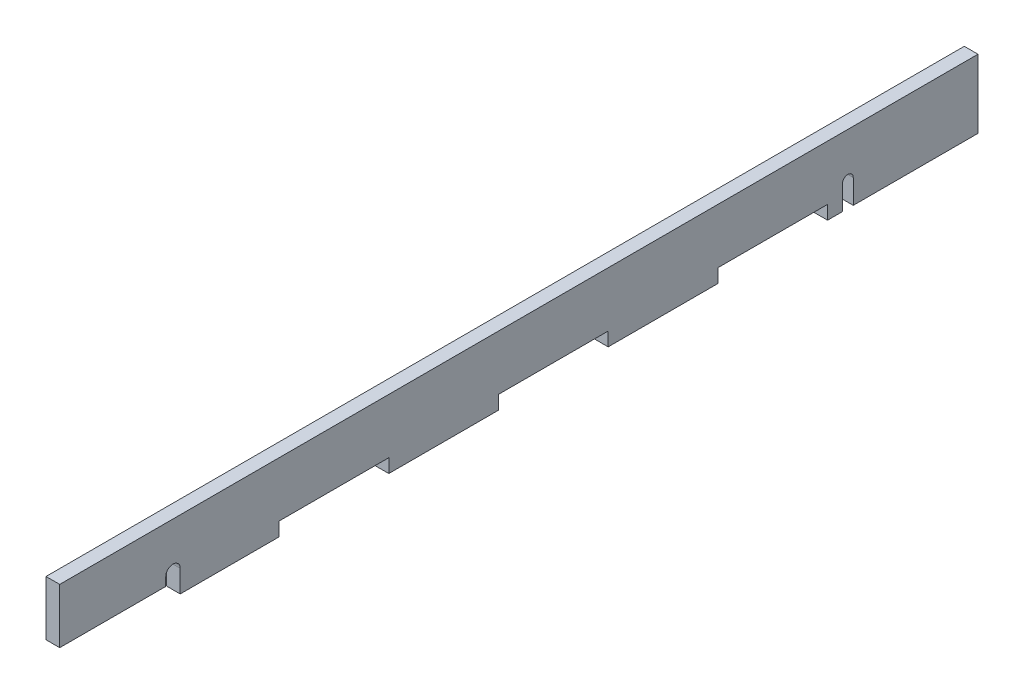
SolidWorks part; units mm, degrees
ref_plane "Front Plane" through (0, 0, 0) normal (0, 0, 1) x (1, 0, 0)
ref_plane "Top Plane" through (0, 0, 0) normal (0, 1, 0) x (1, 0, 0)
ref_plane "Right Plane" through (0, 0, 0) normal (1, 0, 0) x (0, 0, -1)
sketch "Sketch2" plane through (0, 0, 0) normal (1, 0, 0) x (0, 0, -1)
  line L30 (48.3194, 0) -> (99.1194, 0)
  line L31 (-2.4806, 6.35) -> (-2.4806, 31.75)
  line L32 (-2.4806, 31.75) -> (422.7895, 31.75)
  line L33 (422.7895, 0) -> (422.7895, 31.75)
  line L45 (422.7895, 31.75) -> (422.7895, 35.3357) construction
  line L46 (353.1194, 6.35) -> (353.1194, 0)
  line L47 (302.3194, 6.35) -> (353.1194, 6.35)
  line L48 (302.3194, 6.35) -> (302.3194, 0)
  line L49 (251.5194, 6.35) -> (251.5194, 0)
  line L50 (200.7194, 6.35) -> (251.5194, 6.35)
  line L51 (200.7194, 6.35) -> (200.7194, 0)
  line L52 (149.9194, 6.35) -> (149.9194, 0)
  line L53 (99.1194, 6.35) -> (149.9194, 6.35)
  line L54 (99.1194, 6.35) -> (99.1194, 0)
  line L55 (48.3194, 6.35) -> (48.3194, 0)
  line L56 (-2.4806, 6.35) -> (48.3194, 6.35)
  line L57 (353.1194, 0) -> (422.7895, 0)
  line L58 (251.5194, 0) -> (302.3194, 0)
  line L59 (149.9194, 0) -> (200.7194, 0)
  dimension "D1" = 50.8
  dimension "D2" = 6.35
extrude "Boss-Extrude1" add sketch "Sketch2" along normal blind 6.35
sketch "Sketch3" plane through (6.35, 0, 0) normal (1, 0, 0) x (0, 0, -1)
  line L0 (353.1194, 6.35) -> (422.7895, 6.35) construction
  line L1 (422.7895, 0) -> (422.7895, 31.75) construction
  line L2 (362.5194, 8.66) -> (362.5194, 6.35) construction
  line L3 (-2.4806, 31.75) -> (-2.4806, 6.35) construction
  line L5 (365.0194, 11.16) -> (365.0194, -0.0346)
  line L6 (360.0194, 11.16) -> (360.0194, -0.0346)
  line L7 (365.0194, -0.0346) -> (360.0194, -0.0346)
  arc A0 (365.0194, 11.16) -> (360.0194, 11.16) centre (362.5194, 11.16) ccw
  dimension "D1" = 5
  dimension "D2" = 2.31
  dimension "D3" = 365
extrude "Cut-Extrude1" cut sketch "Sketch3" against normal up to next
sketch "Sketch4" plane through (6.35, 0, 0) normal (1, 0, 0) x (0, 0, -1)
  line L1 (53.3194, 10.31) -> (53.3194, 0)
  line L2 (48.3194, 6.35) -> (48.3194, 0)
  line L3 (53.3194, 0) -> (48.3194, 0)
  line L4 (48.3194, 0) -> (99.1194, 0) construction
  line L6 (-2.4806, 6.35) -> (48.3194, 6.35) construction
  line L7 (48.3194, 6.35) -> (48.3194, 0) construction
  line L9 (48.3194, 6.35) -> (46.6194, 6.35)
  line L10 (46.6194, 10.31) -> (46.6194, 6.35)
  arc A1 (53.3194, 10.31) -> (46.6194, 10.31) centre (49.9694, 10.31) ccw
  point P1 (49.9694, 13.66)
  dimension "D1" = 7.31
  dimension "D2" = 1.7
  dimension "D4" = 5
extrude "Cut-Extrude2" cut sketch "Sketch4" against normal through all
